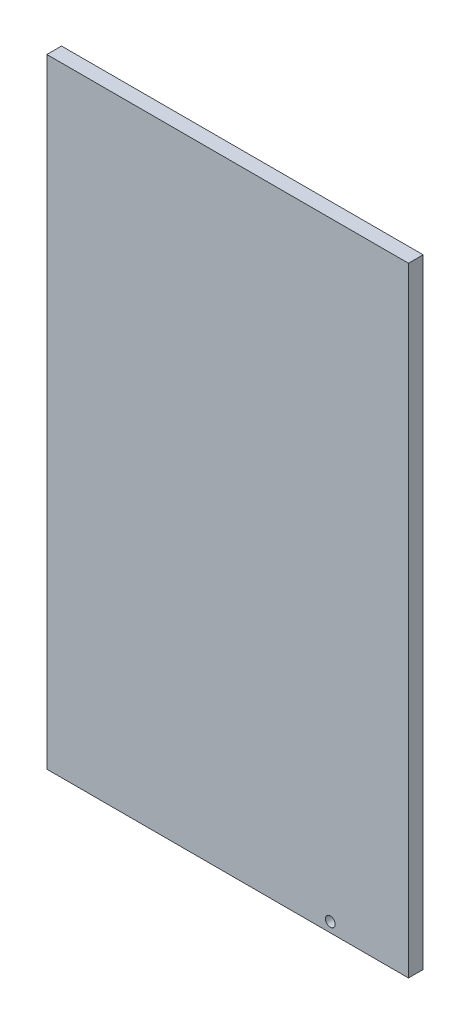
SolidWorks part; units mm, degrees
material "Perspex (TM) GS Acrylic Cast Sheet"
ref_plane "Front Plane" through (0, 0, 0) normal (0, 0, 1) x (1, 0, 0)
ref_plane "Top Plane" through (0, 0, 0) normal (0, 1, 0) x (1, 0, 0)
ref_plane "Right Plane" through (0, 0, 0) normal (1, 0, 0) x (0, 0, -1)
sketch "Sketch1" plane through (0, 0, 0) normal (0, 0, 1) x (1, 0, 0)
  line L1 (-111, -190) -> (111, -190)
  line L2 (-111, -190) -> (-111, 190)
  line L3 (-111, 190) -> (111, 190)
  line L4 (111, -190) -> (111, 190)
  line L5 (-111, -190) -> (111, 190) construction
  line L6 (-111, 190) -> (111, -190) construction
  point P0 (0, 0)
  dimension "D1" = 222
  dimension "D2" = 380
extrude "Boss-Extrude1" add sketch "Sketch1" along normal blind 9
sketch "Sketch2" plane through (0, 0, 9) normal (0, 0, 1) x (1, 0, 0)
  line L0 (111, -190) -> (111, 190) construction
  line L1 (-111, -190) -> (111, -190) construction
  circle A0 centre (63, -184) radius 3
  dimension "D1" = 6
  dimension "D2" = 48
  dimension "D3" = 6
extrude "Cut-Extrude1" cut sketch "Sketch2" against normal through all
sketch "Sketch4" [suppressed] plane through (0, 0, 0) normal (0, 0, -1) x (-1, 0, 0)
  circle A0 centre (-32.16, -180) radius 5.5
  circle A1 centre (-88, -180) radius 5.5
  circle A2 centre (31.84, -180) radius 5.5
  circle A3 centre (87.68, -180) radius 5.5
  dimension "D1" = 11
extrude "Cut-Extrude2" [suppressed] cut sketch "Sketch4" against normal through all
equation "\"PCLength\"= 145mm'Length across I/O from PS to GPU"
equation "\"PCWidth\"= 340mm'Distance of longest part parallel to GPU(ussually GPU)"
equation "\"PCHeight\"= 180mm'Tallest point with mobo laying flat"
equation "\"WallThickness\"= 9mm'Thickness of each outer tank wall"
equation "\"ThermoBarrierThickness\"= 6mm'Thickness of barrier between hot side and cold side"
equation "\"HotSideGap\"= 36mm'Space in the hot side for a pump"
equation "\"PCClearance\"= 40mm'Clearance from top of tank to top of PC"
equation "\"RadiatorHeight\"= 277.37mm'Final Height from ground of radiators"
equation "\"D1@Sketch1\"=\"PCHeight\" + \"ThermoBarrierThickness\" + \"HotSideGap\""
equation "\"D2@Sketch1\"=\"PCWidth\" + \"PCClearance\""
equation "\"D1@Boss-Extrude1\"=\"WallThickness\""
equation "\"D2@Sketch2\"=\"HotSideGap\" + \"ThermoBarrierThickness\" + 6"
